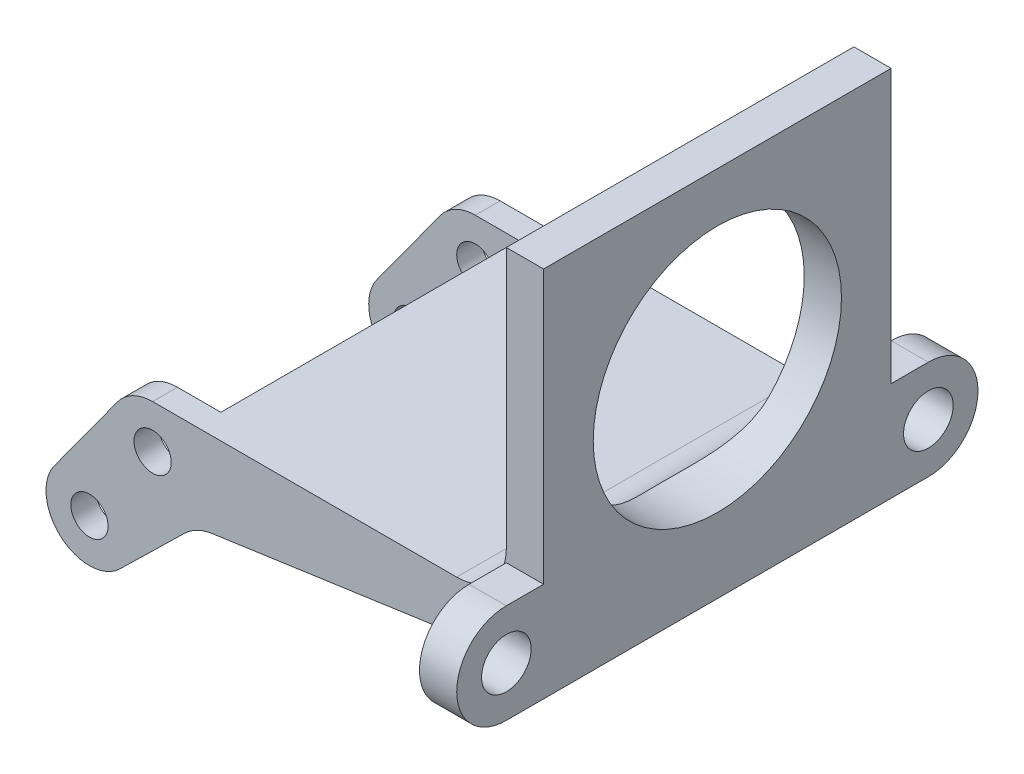
SolidWorks part; units mm, degrees
note: The reader was unsure of these and kept them because the rebuilt part matched: shared geometry of "Sketch4<2>".
ref_plane "Front Plane" through (0, 0, 0) normal (0, 0, 1) x (1, 0, 0)
ref_plane "Top Plane" through (0, 0, 0) normal (0, 1, 0) x (1, 0, 0)
ref_plane "Right Plane" through (0, 0, 0) normal (1, 0, 0) x (0, 0, -1)
sketch "Sketch2" plane through (0, 0, 0) normal (0, 0, 1) x (1, 0, 0)
  circle A0 centre (0, 0) radius 1.5
  circle A1 centre (0, 0) radius 3.5
  dimension "D1" = 3
  dimension "D2" = 2
extrude "Boss-Extrude1" add sketch "Sketch2" along normal blind 2
sketch "Sketch3" plane through (0, 0, 2) normal (0, 0, 1) x (1, 0, 0)
  line L0 (0, 3.5) -> (3.5, 3.5)
  line L1 (3.5, 3.5) -> (3.5, 0)
  line L2 (3.5, 0) -> (3.5, -3.5)
  line L3 (3.5, -3.5) -> (0, -3.5)
  circle A0 centre (0, 0) radius 3.5 construction
  circle A2 centre (0, 0) radius 3.5
  circle M4 centre (0, 0) radius 3.5
extrude "Boss-Extrude2" add sketch "Sketch3" along direction (0, 0, 1) on the side against the normal up to surface (2 mm away) contours L1 L0 M4 | L3 L2 M4
sketch "Sketch4" plane through (0, 0, 2) normal (0, 0, 1) x (1, 0, 0)
  line L0 (-2.8308, 2.0583) -> (-7.9206, -4.9417)
  line L1 (3.5, 3.5) -> (3.5, -3.5)
  line L2 (3.5, -3.5) -> (-2.6438, -9.5033)
  line L3 (3.5, 3.5) -> (0, 3.5)
  circle A0 centre (-5.0899, -7) radius 1.5 construction
  circle A1 centre (-5.0899, -7) radius 1.5
  arc A2 (-7.9206, -4.9417) -> (-2.6438, -9.5033) centre (-5.0899, -7) ccw
  arc A3 (0, 3.5) -> (0, -3.5) centre (0, 0) ccw construction
  arc A4 (0, 3.5) -> (-2.8308, 2.0583) centre (0, 0) ccw
  circle A5 centre (-5.0899, -7) radius 3.5 construction
  circle A6 centre (0, 0) radius 1.5 construction
  circle A7 centre (0, 0) radius 1.5
  point P15 (-2.0725, -10.25)
  dimension "D1" = 2
extrude "Boss-Extrude3" add sketch "Sketch4" against normal up to surface (2 mm away) up to face at (0.875, 0, 0)
extrude "Boss-Extrude4" add sketch "Sketch4<2>" against normal blind 2 from surface at -26 separate body
sketch "Sketch4<2>" plane through (0, 0, 2) normal (0, 0, 1) x (1, 0, 0) same geometry as "Sketch4"
sketch "Sketch5" plane through (0, 0, 2) normal (0, 0, 1) x (1, 0, 0)
  line L0 (3.5, 3.5) -> (28.5, 3.5)
  line L1 (28.5, 3.5) -> (28.5, 28.5)
  line L2 (28.5, 28.5) -> (31.5, 28.5)
  line L3 (31.5, 28.5) -> (31.5, 0.5)
  line L4 (31.5, 0.5) -> (3.5, -3.5)
  line L5 (3.5, 3.5) -> (3.5, -3.5)
  dimension "D1" = 3
  dimension "D2" = 3
  dimension "D3" = 25
  dimension "D4" = 25
extrude "Boss-Extrude5" add sketch "Sketch5" against normal up to surface (28 mm away)
fillet "Fillet1" radius 4 3 edges at (3.5, -3.5, 1) (3.5, -3.5, -25) (28.5, 3.5, -12)
sketch "Sketch6" plane through (31.5, 0, 0) normal (1, 0, 0) x (0, 0, -1)
  line L0 (26, 28.5) -> (-2, 28.5) construction
  line L1 (-2, 0.5) -> (-2, 28.5) construction
  line L2 (26, 28.5) -> (26, 0.5) construction
  circle A0 centre (12, 14.5) radius 10
  circle A1 centre (12, 14.5) radius 14 construction
  dimension "D1" = 20
extrude "Cut-Extrude1" cut sketch "Sketch6" against normal up to next
sketch "Sketch7" plane through (31.5, 0, 0) normal (1, 0, 0) x (0, 0, -1)
  line L0 (-5, 2.5) -> (29, 2.5) construction
  line L1 (26, 0.5) -> (-2, 0.5) construction
  line L2 (-5, 6.5) -> (6, 6.5)
  line L3 (29, -1.5) -> (-5, -1.5)
  line L4 (18, 6.5) -> (29, 6.5)
  line L5 (44.547, 15.7702) -> (56.9145, 15.7702)
  circle A0 centre (-5, 2.5) radius 2
  circle A1 centre (29, 2.5) radius 2
  arc A2 (29, -1.5) -> (29, 6.5) centre (29, 2.5) ccw
  arc A3 (-5, 6.5) -> (-5, -1.5) centre (-5, 2.5) ccw
  arc A4 (6, 6.5) -> (18, 6.5) centre (12, 14.5) ccw
  circle A5 centre (-5, 2.5) radius 4 construction
  circle A6 centre (29, 2.5) radius 4 construction
  circle A7 centre (12, 14.5) radius 10 construction
  arc A8 (56.9145, 8.6325) -> (56.9145, 15.7702) centre (56.9145, 12.2014) ccw
  point P6 (12, 0.5)
  point P7 (12, 2.5)
  point P11 (32.5795, 2.0795)
  point P16 (-1.4205, 2.0795)
  circle M6 centre (12, 14.5) radius 10
  line M7 (26, 0.5) -> (26, 28.5)
  line M9 (-2, 28.5) -> (-2, 0.5)
  line M10 (-2, 0.5) -> (26, 0.5)
  dimension "D3" = 4
  dimension "D1" = 34
  dimension "D2" = 2
extrude "Boss-Extrude6" add sketch "Sketch7" against normal up to surface (3 mm away) contours L4 L2 M6 M9 M10 M7 | L2 A3 L3 A2 L4 A0 A1 M7 M10 M9 up to face at (28.5, 17.3333, -12)
